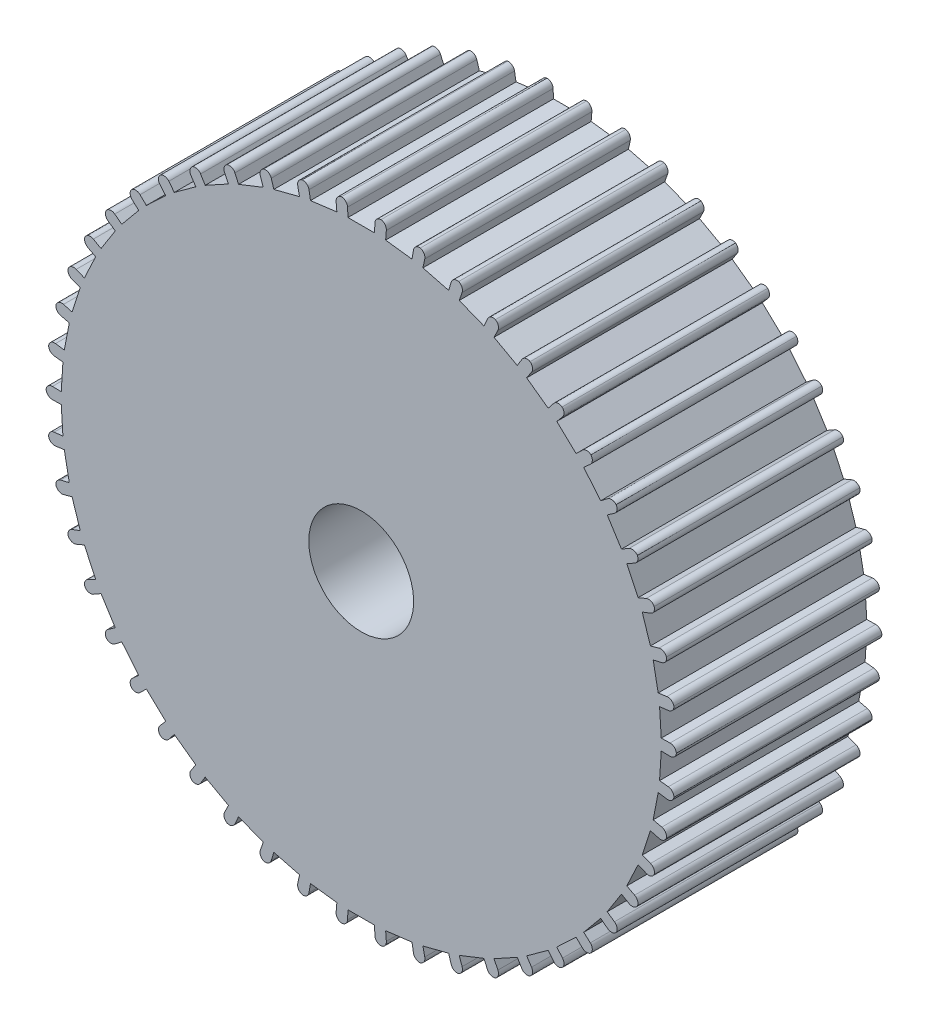
SolidWorks part; units mm, degrees
ref_plane "Front" through (0, 0, 0) normal (0, 0, 1) x (1, 0, 0)
ref_plane "Top" through (0, 0, 0) normal (0, 1, 0) x (1, 0, 0)
ref_plane "Right" through (0, 0, 0) normal (1, 0, 0) x (0, 0, -1)
sketch "Sketch1" plane through (0, 0, 0) normal (0, 0, 1) x (1, 0, 0)
  line L30 (-0.6744, -15.2297) -> (-0.6783, -15.3191)
  line L31 (0.6744, -15.2297) -> (0.6783, -15.3191)
  line L32 (0, -14.5841) -> (0, -15.3341) construction
  line L33 (-0.6783, -15.3191) -> (-1.2471, -15.2833)
  line L34 (-2.5778, -15.0251) -> (-2.5929, -15.1133)
  line L35 (-1.2397, -15.1941) -> (-1.2471, -15.2833)
  line L36 (-2.5929, -15.1133) -> (-3.1528, -15.0065)
  line L37 (-1.8279, -14.4691) -> (-1.9219, -15.2132) construction
  line L38 (-4.4406, -14.5835) -> (-4.4667, -14.6692)
  line L39 (-3.1343, -14.9189) -> (-3.1528, -15.0065)
  line L40 (-4.4667, -14.6692) -> (-5.0087, -14.4931)
  line L41 (-3.6269, -14.1259) -> (-3.8134, -14.8524) construction
  line L42 (-6.2334, -13.912) -> (-6.27, -13.9937)
  line L43 (-4.9794, -14.4085) -> (-5.0087, -14.4931)
  line L44 (-6.27, -13.9937) -> (-6.7857, -13.751)
  line L45 (-5.3688, -13.56) -> (-5.6449, -14.2573) construction
  line L46 (-7.9279, -13.021) -> (-7.9744, -13.0975)
  line L47 (-6.746, -13.6708) -> (-6.7857, -13.751)
  line L48 (-7.9744, -13.0975) -> (-8.4556, -12.7921)
  line L49 (-7.026, -12.7802) -> (-7.3873, -13.4374) construction
  line L50 (-9.4974, -11.9247) -> (-9.5531, -11.9948)
  line L51 (-8.4062, -12.7175) -> (-8.4556, -12.7921)
  line L52 (-9.5531, -11.9948) -> (-9.9922, -11.6315)
  line L53 (-8.5723, -11.7988) -> (-9.0132, -12.4056) construction
  line L54 (-10.917, -10.6403) -> (-10.9811, -10.7029)
  line L55 (-9.9339, -11.5636) -> (-9.9922, -11.6315)
  line L56 (-10.9811, -10.7029) -> (-11.3713, -10.2874)
  line L57 (-9.9835, -10.6314) -> (-10.4969, -11.1781) construction
  line L58 (-12.1645, -9.1882) -> (-12.2359, -9.2422)
  line L59 (-11.3048, -10.2274) -> (-11.3713, -10.2874)
  line L60 (-12.2359, -9.2422) -> (-12.5709, -8.7811)
  line L61 (-11.2373, -9.2963) -> (-11.8152, -9.7743) construction
  line L62 (-13.2202, -7.5911) -> (-13.2978, -7.6357)
  line L63 (-12.4975, -8.7299) -> (-12.5709, -8.7811)
  line L64 (-13.2978, -7.6357) -> (-13.5724, -7.1363)
  line L65 (-12.3138, -7.8146) -> (-12.947, -8.2164) construction
  line L66 (-14.0674, -5.8743) -> (-14.15, -5.9089)
  line L67 (-13.4931, -7.0947) -> (-13.5724, -7.1363)
  line L68 (-14.15, -5.9089) -> (-14.3598, -5.3789)
  line L69 (-13.1961, -6.2096) -> (-13.8747, -6.529) construction
  line L70 (-14.6927, -4.0649) -> (-14.779, -4.0888)
  line L71 (-14.2759, -5.3476) -> (-14.3598, -5.3789)
  line L72 (-14.779, -4.0888) -> (-14.9207, -3.5368)
  line L73 (-13.8703, -4.5067) -> (-14.5836, -4.7385) construction
  line L74 (-15.0863, -2.1913) -> (-15.1749, -2.2043)
  line L75 (-14.8336, -3.5162) -> (-14.9207, -3.5368)
  line L76 (-15.1749, -2.2043) -> (-15.2463, -1.6388)
  line L77 (-14.3258, -2.7328) -> (-15.0625, -2.8733) construction
  line L78 (-15.242, -0.2833) -> (-15.3315, -0.285)
  line L79 (-15.1573, -1.6293) -> (-15.2463, -1.6388)
  line L80 (-15.3315, -0.285) -> (-15.3315, 0.285)
  line L81 (-14.5554, -0.9157) -> (-15.3039, -0.9628) construction
  line L82 (-15.1573, 1.6293) -> (-15.2463, 1.6388)
  line L83 (-15.242, 0.2833) -> (-15.3315, 0.285)
  line L84 (-15.2463, 1.6388) -> (-15.1749, 2.2043)
  line L85 (-14.5554, 0.9157) -> (-15.3039, 0.9628) construction
  line L86 (-14.8336, 3.5162) -> (-14.9207, 3.5368)
  line L87 (-15.0863, 2.1913) -> (-15.1749, 2.2043)
  line L88 (-14.9207, 3.5368) -> (-14.779, 4.0888)
  line L89 (-14.3258, 2.7328) -> (-15.0625, 2.8733) construction
  line L90 (-14.2759, 5.3476) -> (-14.3598, 5.3789)
  line L91 (-14.6927, 4.0649) -> (-14.779, 4.0888)
  line L92 (-14.3598, 5.3789) -> (-14.15, 5.9089)
  line L93 (-13.8703, 4.5067) -> (-14.5836, 4.7385) construction
  line L94 (-13.4931, 7.0947) -> (-13.5724, 7.1363)
  line L95 (-14.0674, 5.8743) -> (-14.15, 5.9089)
  line L96 (-13.5724, 7.1363) -> (-13.2978, 7.6357)
  line L97 (-13.1961, 6.2096) -> (-13.8747, 6.529) construction
  line L98 (-12.4975, 8.7299) -> (-12.5709, 8.7811)
  line L99 (-13.2202, 7.5911) -> (-13.2978, 7.6357)
  line L100 (-12.5709, 8.7811) -> (-12.2359, 9.2422)
  line L101 (-12.3138, 7.8146) -> (-12.947, 8.2164) construction
  line L102 (-11.3048, 10.2274) -> (-11.3713, 10.2874)
  line L103 (-12.1645, 9.1882) -> (-12.2359, 9.2422)
  line L104 (-11.3713, 10.2874) -> (-10.9811, 10.7029)
  line L105 (-11.2373, 9.2963) -> (-11.8152, 9.7743) construction
  line L106 (-9.9339, 11.5636) -> (-9.9922, 11.6315)
  line L107 (-10.917, 10.6403) -> (-10.9811, 10.7029)
  line L108 (-9.9922, 11.6315) -> (-9.5531, 11.9948)
  line L109 (-9.9835, 10.6314) -> (-10.4969, 11.1781) construction
  line L110 (-8.4062, 12.7175) -> (-8.4556, 12.7921)
  line L111 (-9.4974, 11.9247) -> (-9.5531, 11.9948)
  line L112 (-8.4556, 12.7921) -> (-7.9744, 13.0975)
  line L113 (-8.5723, 11.7988) -> (-9.0132, 12.4056) construction
  line L114 (-6.746, 13.6708) -> (-6.7857, 13.751)
  line L115 (-7.9279, 13.021) -> (-7.9744, 13.0975)
  line L116 (-6.7857, 13.751) -> (-6.27, 13.9937)
  line L117 (-7.026, 12.7802) -> (-7.3873, 13.4374) construction
  line L118 (-4.9794, 14.4085) -> (-5.0087, 14.4931)
  line L119 (-6.2334, 13.912) -> (-6.27, 13.9937)
  line L120 (-5.0087, 14.4931) -> (-4.4667, 14.6692)
  line L121 (-5.3688, 13.56) -> (-5.6449, 14.2573) construction
  line L122 (-3.1343, 14.9189) -> (-3.1528, 15.0065)
  line L123 (-4.4406, 14.5835) -> (-4.4667, 14.6692)
  line L124 (-3.1528, 15.0065) -> (-2.5929, 15.1133)
  line L125 (-3.6269, 14.1259) -> (-3.8134, 14.8524) construction
  line L126 (-1.2397, 15.1941) -> (-1.2471, 15.2833)
  line L127 (-2.5778, 15.0251) -> (-2.5929, 15.1133)
  line L128 (-1.2471, 15.2833) -> (-0.6783, 15.3191)
  line L129 (-1.8279, 14.4691) -> (-1.9219, 15.2132) construction
  line L130 (0.6744, 15.2297) -> (0.6783, 15.3191)
  line L131 (-0.6744, 15.2297) -> (-0.6783, 15.3191)
  line L132 (0.6783, 15.3191) -> (1.2471, 15.2833)
  line L133 (0, 14.5841) -> (0, 15.3341) construction
  line L134 (2.5778, 15.0251) -> (2.5929, 15.1133)
  line L135 (1.2397, 15.1941) -> (1.2471, 15.2833)
  line L136 (2.5929, 15.1133) -> (3.1528, 15.0065)
  line L137 (1.8279, 14.4691) -> (1.9219, 15.2132) construction
  line L138 (4.4406, 14.5835) -> (4.4667, 14.6692)
  line L139 (3.1343, 14.9189) -> (3.1528, 15.0065)
  line L140 (4.4667, 14.6692) -> (5.0087, 14.4931)
  line L141 (3.6269, 14.1259) -> (3.8134, 14.8524) construction
  line L142 (6.2334, 13.912) -> (6.27, 13.9937)
  line L143 (4.9794, 14.4085) -> (5.0087, 14.4931)
  line L144 (6.27, 13.9937) -> (6.7857, 13.751)
  line L145 (5.3688, 13.56) -> (5.6449, 14.2573) construction
  line L146 (7.9279, 13.021) -> (7.9744, 13.0975)
  line L147 (6.746, 13.6708) -> (6.7857, 13.751)
  line L148 (7.9744, 13.0975) -> (8.4556, 12.7921)
  line L149 (7.026, 12.7802) -> (7.3873, 13.4374) construction
  line L150 (0, 0) -> (0, -14.5841) construction
  line L151 (9.4974, 11.9247) -> (9.5531, 11.9948)
  line L152 (8.4062, 12.7175) -> (8.4556, 12.7921)
  line L153 (9.5531, 11.9948) -> (9.9922, 11.6315)
  line L154 (8.5723, 11.7988) -> (9.0132, 12.4056) construction
  line L155 (10.917, 10.6403) -> (10.9811, 10.7029)
  line L156 (9.9339, 11.5636) -> (9.9922, 11.6315)
  line L157 (10.9811, 10.7029) -> (11.3713, 10.2874)
  line L158 (9.9835, 10.6314) -> (10.4969, 11.1781) construction
  line L159 (12.1645, 9.1882) -> (12.2359, 9.2422)
  line L160 (11.3048, 10.2274) -> (11.3713, 10.2874)
  line L161 (12.2359, 9.2422) -> (12.5709, 8.7811)
  line L162 (11.2373, 9.2963) -> (11.8152, 9.7743) construction
  line L163 (13.2202, 7.5911) -> (13.2978, 7.6357)
  line L164 (12.4975, 8.7299) -> (12.5709, 8.7811)
  line L165 (13.2978, 7.6357) -> (13.5724, 7.1363)
  line L166 (12.3138, 7.8146) -> (12.947, 8.2164) construction
  line L167 (14.0674, 5.8743) -> (14.15, 5.9089)
  line L168 (13.4931, 7.0947) -> (13.5724, 7.1363)
  line L169 (14.15, 5.9089) -> (14.3598, 5.3789)
  line L170 (13.1961, 6.2096) -> (13.8747, 6.529) construction
  line L171 (14.6927, 4.0649) -> (14.779, 4.0888)
  line L172 (14.2759, 5.3476) -> (14.3598, 5.3789)
  line L173 (14.779, 4.0888) -> (14.9207, 3.5368)
  line L174 (13.8703, 4.5067) -> (14.5836, 4.7385) construction
  line L175 (15.0863, 2.1913) -> (15.1749, 2.2043)
  line L176 (14.8336, 3.5162) -> (14.9207, 3.5368)
  line L177 (15.1749, 2.2043) -> (15.2463, 1.6388)
  line L178 (14.3258, 2.7328) -> (15.0625, 2.8733) construction
  line L179 (15.242, 0.2833) -> (15.3315, 0.285)
  line L180 (15.1573, 1.6293) -> (15.2463, 1.6388)
  line L181 (15.3315, 0.285) -> (15.3315, -0.285)
  line L182 (14.5554, 0.9157) -> (15.3039, 0.9628) construction
  line L183 (15.1573, -1.6293) -> (15.2463, -1.6388)
  line L184 (15.242, -0.2833) -> (15.3315, -0.285)
  line L185 (15.2463, -1.6388) -> (15.1749, -2.2043)
  line L186 (14.5554, -0.9157) -> (15.3039, -0.9628) construction
  line L187 (14.8336, -3.5162) -> (14.9207, -3.5368)
  line L188 (15.0863, -2.1913) -> (15.1749, -2.2043)
  line L189 (14.9207, -3.5368) -> (14.779, -4.0888)
  line L190 (14.3258, -2.7328) -> (15.0625, -2.8733) construction
  line L191 (14.2759, -5.3476) -> (14.3598, -5.3789)
  line L192 (14.6927, -4.0649) -> (14.779, -4.0888)
  line L193 (14.3598, -5.3789) -> (14.15, -5.9089)
  line L194 (13.8703, -4.5067) -> (14.5836, -4.7385) construction
  line L195 (13.4931, -7.0947) -> (13.5724, -7.1363)
  line L196 (14.0674, -5.8743) -> (14.15, -5.9089)
  line L197 (13.5724, -7.1363) -> (13.2978, -7.6357)
  line L198 (13.1961, -6.2096) -> (13.8747, -6.529) construction
  line L199 (12.4975, -8.7299) -> (12.5709, -8.7811)
  line L200 (13.2202, -7.5911) -> (13.2978, -7.6357)
  line L201 (12.5709, -8.7811) -> (12.2359, -9.2422)
  line L202 (12.3138, -7.8146) -> (12.947, -8.2164) construction
  line L203 (11.3048, -10.2274) -> (11.3713, -10.2874)
  line L204 (12.1645, -9.1882) -> (12.2359, -9.2422)
  line L205 (11.3713, -10.2874) -> (10.9811, -10.7029)
  line L206 (11.2373, -9.2963) -> (11.8152, -9.7743) construction
  line L207 (9.9339, -11.5636) -> (9.9922, -11.6315)
  line L208 (10.917, -10.6403) -> (10.9811, -10.7029)
  line L209 (9.9922, -11.6315) -> (9.5531, -11.9948)
  line L210 (9.9835, -10.6314) -> (10.4969, -11.1781) construction
  line L211 (8.4062, -12.7175) -> (8.4556, -12.7921)
  line L212 (9.4974, -11.9247) -> (9.5531, -11.9948)
  line L213 (8.4556, -12.7921) -> (7.9744, -13.0975)
  line L214 (8.5723, -11.7988) -> (9.0132, -12.4056) construction
  line L215 (6.746, -13.6708) -> (6.7857, -13.751)
  line L216 (7.9279, -13.021) -> (7.9744, -13.0975)
  line L217 (6.7857, -13.751) -> (6.27, -13.9937)
  line L218 (7.026, -12.7802) -> (7.3873, -13.4374) construction
  line L219 (4.9794, -14.4085) -> (5.0087, -14.4931)
  line L220 (6.2334, -13.912) -> (6.27, -13.9937)
  line L221 (5.0087, -14.4931) -> (4.4667, -14.6692)
  line L222 (5.3688, -13.56) -> (5.6449, -14.2573) construction
  line L223 (3.1343, -14.9189) -> (3.1528, -15.0065)
  line L224 (4.4406, -14.5835) -> (4.4667, -14.6692)
  line L225 (3.1528, -15.0065) -> (2.5929, -15.1133)
  line L226 (3.6269, -14.1259) -> (3.8134, -14.8524) construction
  line L227 (1.2397, -15.1941) -> (1.2471, -15.2833)
  line L228 (2.5778, -15.0251) -> (2.5929, -15.1133)
  line L229 (1.2471, -15.2833) -> (0.6783, -15.3191)
  line L230 (1.8279, -14.4691) -> (1.9219, -15.2132) construction
  circle A31 centre (0, 0) radius 15.3341 construction
  arc A32 (-0.6744, -15.2297) -> (0.6744, -15.2297) centre (0, -15.2591) cw
  arc A33 (-2.5778, -15.0251) -> (-1.2397, -15.1941) centre (-1.9125, -15.1388) cw
  arc A34 (-4.4406, -14.5835) -> (-3.1343, -14.9189) centre (-3.7948, -14.7797) cw
  arc A35 (-6.2334, -13.912) -> (-4.9794, -14.4085) centre (-5.6173, -14.1876) cw
  arc A36 (-7.9279, -13.021) -> (-6.746, -13.6708) centre (-7.3511, -13.3717) cw
  arc A37 (-9.4974, -11.9247) -> (-8.4062, -12.7175) centre (-8.9691, -12.3449) cw
  arc A38 (-10.917, -10.6403) -> (-9.9339, -11.5636) centre (-10.4456, -11.1234) cw
  arc A39 (-12.1645, -9.1882) -> (-11.3048, -10.2274) centre (-11.7574, -9.7265) cw
  arc A40 (-13.2202, -7.5911) -> (-12.4975, -8.7299) centre (-12.8837, -8.1763) cw
  arc A41 (-14.0674, -5.8743) -> (-13.4931, -7.0947) centre (-13.8069, -6.497) cw
  arc A42 (-14.6927, -4.0649) -> (-14.2759, -5.3476) centre (-14.5123, -4.7153) cw
  arc A43 (-15.0863, -2.1913) -> (-14.8336, -3.5162) centre (-14.9889, -2.8593) cw
  arc A44 (-15.242, -0.2833) -> (-15.1573, -1.6293) centre (-15.229, -0.9581) cw
  arc A45 (-15.1573, 1.6293) -> (-15.242, 0.2833) centre (-15.229, 0.9581) cw
  arc A46 (-14.8336, 3.5162) -> (-15.0863, 2.1913) centre (-14.9889, 2.8593) cw
  arc A47 (-14.2759, 5.3476) -> (-14.6927, 4.0649) centre (-14.5123, 4.7153) cw
  arc A48 (-13.4931, 7.0947) -> (-14.0674, 5.8743) centre (-13.8069, 6.497) cw
  arc A49 (-12.4975, 8.7299) -> (-13.2202, 7.5911) centre (-12.8837, 8.1763) cw
  arc A50 (-11.3048, 10.2274) -> (-12.1645, 9.1882) centre (-11.7574, 9.7265) cw
  arc A51 (-9.9339, 11.5636) -> (-10.917, 10.6403) centre (-10.4456, 11.1234) cw
  arc A52 (-8.4062, 12.7175) -> (-9.4974, 11.9247) centre (-8.9691, 12.3449) cw
  arc A53 (-6.746, 13.6708) -> (-7.9279, 13.021) centre (-7.3511, 13.3717) cw
  arc A54 (-4.9794, 14.4085) -> (-6.2334, 13.912) centre (-5.6173, 14.1876) cw
  arc A55 (-3.1343, 14.9189) -> (-4.4406, 14.5835) centre (-3.7948, 14.7797) cw
  arc A56 (-1.2397, 15.1941) -> (-2.5778, 15.0251) centre (-1.9125, 15.1388) cw
  arc A57 (0.6744, 15.2297) -> (-0.6744, 15.2297) centre (0, 15.2591) cw
  arc A58 (2.5778, 15.0251) -> (1.2397, 15.1941) centre (1.9125, 15.1388) cw
  arc A59 (4.4406, 14.5835) -> (3.1343, 14.9189) centre (3.7948, 14.7797) cw
  arc A60 (6.2334, 13.912) -> (4.9794, 14.4085) centre (5.6173, 14.1876) cw
  arc A61 (7.9279, 13.021) -> (6.746, 13.6708) centre (7.3511, 13.3717) cw
  arc A62 (9.4974, 11.9247) -> (8.4062, 12.7175) centre (8.9691, 12.3449) cw
  arc A63 (10.917, 10.6403) -> (9.9339, 11.5636) centre (10.4456, 11.1234) cw
  arc A64 (12.1645, 9.1882) -> (11.3048, 10.2274) centre (11.7574, 9.7265) cw
  arc A65 (13.2202, 7.5911) -> (12.4975, 8.7299) centre (12.8837, 8.1763) cw
  arc A66 (14.0674, 5.8743) -> (13.4931, 7.0947) centre (13.8069, 6.497) cw
  arc A73 (-1.9219, -15.2132) -> (0, -15.3341) centre (0, 0) ccw construction
  arc A74 (14.6927, 4.0649) -> (14.2759, 5.3476) centre (14.5123, 4.7153) cw
  arc A75 (15.0863, 2.1913) -> (14.8336, 3.5162) centre (14.9889, 2.8593) cw
  arc A76 (15.242, 0.2833) -> (15.1573, 1.6293) centre (15.229, 0.9581) cw
  arc A77 (15.1573, -1.6293) -> (15.242, -0.2833) centre (15.229, -0.9581) cw
  arc A78 (14.8336, -3.5162) -> (15.0863, -2.1913) centre (14.9889, -2.8593) cw
  arc A79 (14.2759, -5.3476) -> (14.6927, -4.0649) centre (14.5123, -4.7153) cw
  arc A80 (13.4931, -7.0947) -> (14.0674, -5.8743) centre (13.8069, -6.497) cw
  arc A81 (12.4975, -8.7299) -> (13.2202, -7.5911) centre (12.8837, -8.1763) cw
  arc A82 (11.3048, -10.2274) -> (12.1645, -9.1882) centre (11.7574, -9.7265) cw
  arc A83 (9.9339, -11.5636) -> (10.917, -10.6403) centre (10.4456, -11.1234) cw
  arc A84 (8.4062, -12.7175) -> (9.4974, -11.9247) centre (8.9691, -12.3449) cw
  arc A85 (6.746, -13.6708) -> (7.9279, -13.021) centre (7.3511, -13.3717) cw
  arc A86 (4.9794, -14.4085) -> (6.2334, -13.912) centre (5.6173, -14.1876) cw
  arc A87 (3.1343, -14.9189) -> (4.4406, -14.5835) centre (3.7948, -14.7797) cw
  arc A88 (1.2397, -15.1941) -> (2.5778, -15.0251) centre (1.9125, -15.1388) cw
  dimension "D1" = 0.675
  dimension "D2" = 0.75
  dimension "D3" = 5
  dimension "D6" = 1.9269
  dimension "D5" = 50
extrude "Boss-Extrude1" add sketch "Sketch1" along normal blind 10 contours L227 A88 L228 L225 L223 A87 L224 L221 L219 A86 L220 L217 L215 A85 L216 L213 L211 A84 L212 L209 L207 A83 L208 L205 L203 A82 L204 L201 L199 A81 L200 L197 L195 A80 L196 L193 L191 A79 L192 L189 L187 A78 L188 L185 L183 A77 L184 L181 L179 A76 L180 region at (0, 0, 0)
sketch "Sketch3" plane through (0, 0, 0) normal (0, 0, -1) x (-1, 0, 0)
  circle A0 centre (0, 0) radius 7.5
  dimension "D1" = 15
extrude "Boss-Extrude2" add sketch "Sketch3" along normal blind 5
sketch "Sketch4" plane through (0, 0, -5) normal (0, 0, -1) x (-1, 0, 0)
  circle A0 centre (0, 0) radius 2.55
  dimension "D1" = 5.1
extrude "Cut-Extrude1" cut sketch "Sketch4" against normal through all
sketch "Sketch6" plane through (0, 0, 0) normal (1, 0, 0) x (0, 0, -1)
  line L0 (5, -7.5) -> (5, 7.5) construction
  circle A0 centre (2.5, 0) radius 1.25
  dimension "D1" = 2.5
  dimension "D2" = 2.5
extrude "Cut-Extrude2" cut sketch "Sketch6" against normal through all both and the other way through all
sketch "Sketch7" plane through (0, 0, 10) normal (0, 0, 1) x (1, 0, 0)
  line L0 (-0.6744, -15.2297) -> (-0.6783, -15.3191) construction
  line L1 (-0.6744, -15.2297) -> (0.6744, -15.2297)
  line L2 (-0.6744, -15.2297) -> (-0.6462, -14.5841)
  line L3 (-0.6462, -14.5841) -> (0.6462, -14.5841)
  line L4 (0.6744, -15.2297) -> (0.6462, -14.5841)
  line L5 (0, -14.5841) -> (0, -15.2297) construction
  line L6 (-0.6603, -14.9069) -> (0.6603, -14.9069) construction
  arc A0 (0.6744, -15.2297) -> (-0.6744, -15.2297) centre (0, -15.2591) ccw construction
  point P4 (0.6744, -15.2297)
  point P5 (0, -14.5841)
  point P9 (-0.4913, -14.5841)
  point P296 (0, -14.9069)
extrude "Cut-Extrude3" cut sketch "Sketch7" against normal through all
pattern_circular "CirPattern1" count 50 over 360 about axis through (0, 0, 10) along (0, 0, -1) of "Cut-Extrude3"
fillet "Fillet1" radius 0.3 100 edges at (1.2471, -15.2833, 5) (0.6783, -15.3191, 5) (-0.6783, -15.3191, 5) (-1.2471, -15.2833, 5) (-2.5929, -15.1133, 5) (-3.1528, -15.0065, 5) (-4.4667, -14.6692, 5) (-5.0087, -14.4931, 5) (-6.27, -13.9937, 5) (-6.7857, -13.751, 5) (-7.9744, -13.0975, 5) (-8.4556, -12.7921, 5) (-9.5531, -11.9948, 5) (-9.9922, -11.6315, 5) (-10.9811, -10.7029, 5) (-11.3713, -10.2874, 5) (-12.2359, -9.2422, 5) (-12.5709, -8.7811, 5) (-13.2978, -7.6357, 5) (-13.5724, -7.1363, 5) (-14.15, -5.9089, 5) (-14.3598, -5.3789, 5) (-14.779, -4.0888, 5) (-14.9207, -3.5368, 5) (-15.1749, -2.2043, 5) (-15.2463, -1.6388, 5) (-15.3315, -0.285, 5) (-15.3315, 0.285, 5) (-15.2463, 1.6388, 5) (-15.1749, 2.2043, 5) (-14.9207, 3.5368, 5) (-14.779, 4.0888, 5) (-14.3598, 5.3789, 5) (-14.15, 5.9089, 5) (-13.5724, 7.1363, 5) (-13.2978, 7.6357, 5) (-12.5709, 8.7811, 5) (-12.2359, 9.2422, 5) (-11.3713, 10.2874, 5) (-10.9811, 10.7029, 5) (-9.9922, 11.6315, 5) (-9.5531, 11.9948, 5) (-8.4556, 12.7921, 5) (-7.9744, 13.0975, 5) (-6.7857, 13.751, 5) (-6.27, 13.9937, 5) (-5.0087, 14.4931, 5) (-4.4667, 14.6692, 5) (-3.1528, 15.0065, 5) (-2.5929, 15.1133, 5) (-1.2471, 15.2833, 5) (-0.6783, 15.3191, 5) (0.6783, 15.3191, 5) (1.2471, 15.2833, 5) (2.5929, 15.1133, 5) (3.1528, 15.0065, 5) (4.4667, 14.6692, 5) (5.0087, 14.4931, 5) (6.27, 13.9937, 5) (6.7857, 13.751, 5) (7.9744, 13.0975, 5) (8.4556, 12.7921, 5) (9.5531, 11.9948, 5) (9.9922, 11.6315, 5) (10.9811, 10.7029, 5) (11.3713, 10.2874, 5) (12.2359, 9.2422, 5) (12.5709, 8.7811, 5) (13.2978, 7.6357, 5) (13.5724, 7.1363, 5) (14.15, 5.9089, 5) (14.3598, 5.3789, 5) (14.779, 4.0888, 5) (14.9207, 3.5368, 5) (15.1749, 2.2043, 5) (15.2463, 1.6388, 5) (15.3315, 0.285, 5) (15.3315, -0.285, 5) (15.2463, -1.6388, 5) (15.1749, -2.2043, 5) (14.9207, -3.5368, 5) (14.779, -4.0888, 5) (14.3598, -5.3789, 5) (14.15, -5.9089, 5) (13.5724, -7.1363, 5) (13.2978, -7.6357, 5) (12.5709, -8.7811, 5) (12.2359, -9.2422, 5) (11.3713, -10.2874, 5) (8.4556, -12.7921, 5) (7.9744, -13.0975, 5) (6.7857, -13.751, 5) (6.27, -13.9937, 5) (5.0087, -14.4931, 5) (4.4667, -14.6692, 5) (3.1528, -15.0065, 5) (2.5929, -15.1133, 5) (10.9811, -10.7029, 5) (9.9922, -11.6315, 5) (9.5531, -11.9948, 5)
